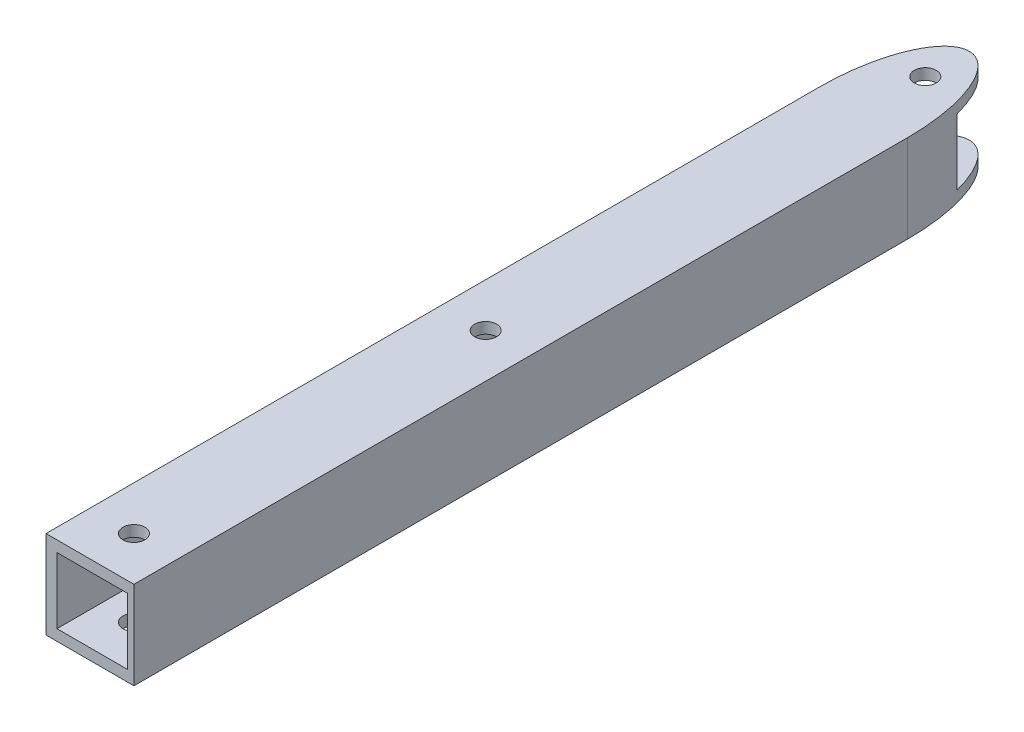
SolidWorks part; units mm, degrees
ref_plane "Front Plane" through (0, 0, 0) normal (0, 0, 1) x (1, 0, 0)
ref_plane "Top Plane" through (0, 0, 0) normal (0, 1, 0) x (1, 0, 0)
ref_plane "Right Plane" through (0, 0, 0) normal (1, 0, 0) x (0, 0, -1)
sketch "Sketch1" plane through (0, 0, 0) normal (0, 0, 1) x (1, 0, 0)
  line L1 (0, 0) -> (25.4, 0)
  line L2 (0, 0) -> (0, 25.4)
  line L3 (0, 25.4) -> (25.4, 25.4)
  line L4 (25.4, 0) -> (25.4, 25.4)
  dimension "D1" = 25.4
  dimension "D2" = 25.4
extrude "Boss-Extrude2" add sketch "Sketch1" along normal blind 254 contours L3 L4 L1 L2
sketch "Sketch2" plane through (0, 0, 0) normal (0, 0, -1) x (-1, 0, 0)
  line L0 (-23.4778, 22.225) -> (-3.175, 22.225)
  line L1 (-23.4778, 22.225) -> (-23.4778, 3.175)
  line L2 (-23.4778, 3.175) -> (-3.175, 3.175)
  line L3 (-3.175, 22.225) -> (-3.175, 3.175)
  line L4 (0, 0) -> (0, 25.4) construction
  line L5 (0, 0) -> (-25.4, 0) construction
  dimension "D1" = 3.175
  dimension "D2" = 3.175
extrude "Cut-Extrude1" cut sketch "Sketch2" against normal through all
sketch "Sketch3" plane through (0, 25.4, 0) normal (0, 1, 0) x (1, 0, 0)
  line L4 (0, 0) -> (25.4, 0) construction
  line L5 (12.7, 0) -> (25.4, 0)
  line L6 (25.4, 0) -> (25.4, -30.4659)
  line L7 (12.7, 0) -> (0, 0)
  line L8 (0, 0) -> (0, -30.4659)
  ellipse E0 centre (12.7, -30.4659) end of major axis (12.7, 0) minor radius 12.7 (25.4, -30.4659) -> (0, -30.4659) ccw
  line M2 (25.4, 0) -> (0, 0)
  line M3 (0, 0) -> (0, -254)
  line M5 (25.4, -254) -> (25.4, 0)
extrude "Cut-Extrude2" cut sketch "Sketch3" against normal through all contours E0 M2 M3 | E0 M5 M2 region at (2.8368, 25.4, 6.8051) region at (22.5632, 25.4, 6.8051)
sketch "Sketch4" plane through (0, 25.4, 0) normal (0, 1, 0) x (1, 0, 0)
  line L0 (25.4, -254) -> (0, -254)
  circle A1 centre (12.7, -139.7) radius 3.175
  dimension "D3" = 6.35
  dimension "D4" = 114.3
sketch "Sketch6" plane through (0, 25.4, 0) normal (0, 1, 0) x (1, 0, 0)
  line L0 (0, 0) -> (25.4, 0)
  circle A0 centre (12.7, -12.7) radius 3.175
  circle A1 centre (12.7, -1206.5) radius 3.175
  point P7 (12.7, 0)
  dimension "D2" = 6.35
  dimension "D3" = 12.7
  dimension "D4" = 6.35
  dimension "D5" = 1206.5
  dimension "D1" = 25.4
extrude "Cut-Extrude5" cut sketch "Sketch6" against normal through all contours A0
extrude "Cut-Extrude6" cut sketch "Sketch4" against normal through all contours A1
sketch "Sketch7" plane through (0, 25.4, 0) normal (0, 1, 0) x (1, 0, 0)
  line L0 (0, -254) -> (25.4, -254) construction
  circle A0 centre (12.7, -241.3) radius 3.175
  point P4 (12.7, -254)
  dimension "D1" = 12.7
extrude "Cut-Extrude7" cut sketch "Sketch7" against normal through all
